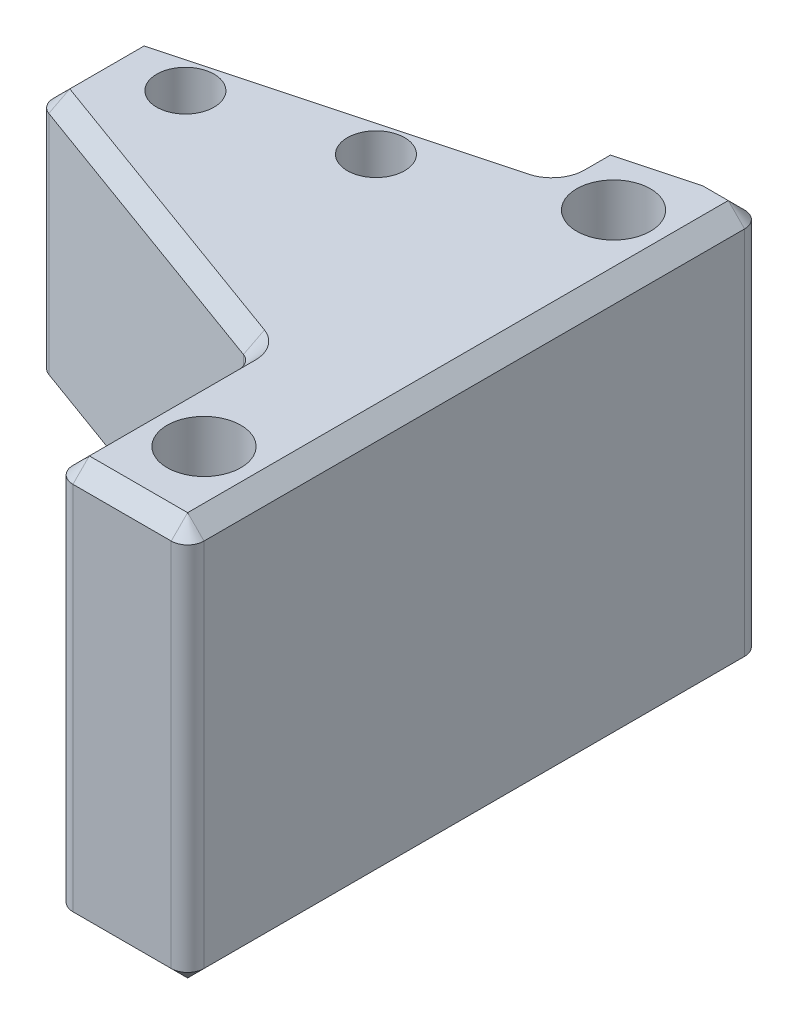
SolidWorks part; units mm, degrees
ref_plane "Front Plane" through (0, 0, 0) normal (0, 0, 1) x (1, 0, 0)
ref_plane "Top Plane" through (0, 0, 0) normal (0, 1, 0) x (1, 0, 0)
ref_plane "Right Plane" through (0, 0, 0) normal (1, 0, 0) x (0, 0, -1)
sketch "Sketch1" plane through (0, 0, 0) normal (0, 1, 0) x (1, 0, 0)
  line L1 (4, -17.5) -> (-4, -17.5)
  line L2 (4, -17.5) -> (4, 17.5)
  line L3 (4, 17.5) -> (-4, 17.5)
  line L4 (-4, -17.5) -> (-4, 17.5)
  line L5 (0, 17.5) -> (0, -17.5) construction
  line L6 (4, 0) -> (-4, 0) construction
  circle A0 centre (0, 12.5) radius 2.25
  circle A1 centre (0, -12.5) radius 2.25
  point P0 (0, 0)
  dimension "D3" = 4.5
  dimension "D1" = 25
  dimension "D2" = 8
  dimension "D4" = 35
extrude "Boss-Extrude1" add sketch "Sketch1" along normal blind 10
sketch "Sketch2" plane through (0, 10, 0) normal (0, 1, 0) x (1, 0, 0)
  line L0 (-8, 15) -> (1.3301, 17.5) construction
  line L1 (0, 14.75) -> (0, 10.25) construction
  line L2 (0, 12.5) -> (2.25, 12.5) construction
  line L3 (-8, 15) -> (-8, -17.5) construction
  line L4 (-8, -17.5) -> (-4, -17.5) construction
  line L5 (4, 17.5) -> (-4, 17.5) construction
  line L6 (-19.3763, 5.7401) -> (-10.2, 8.1989) construction
  line L7 (-4, 17.5) -> (-4, -17.5) construction
  line L8 (-4, -5.6724) -> (-24, 1.607)
  line L9 (-24, 1.607) -> (-24, 7.607)
  line L10 (-24, 7.607) -> (-4, 12.966)
  line L11 (-4, 12.966) -> (-4, -5.6724)
  line L12 (1.3301, 17.5) -> (-4, 17.5)
  line L13 (-4, 17.5) -> (-4, 16.0718)
  line L14 (-4, 16.0718) -> (1.3301, 17.5)
  circle A0 centre (0, 12.5) radius 2.25 construction
  circle A1 centre (-10.2, 8.1989) radius 1.75
  circle A2 centre (-19.3763, 5.7401) radius 1.75
  point P7 (0, 12.5)
  point P23 (-4, 0)
  point P29 (0, 0)
  point P30 (-4, -2.9492)
  point P31 (-21.9255, 6.9595)
  point P32 (-4, -4.1892)
  line M11 (-4, 17.5) -> (-4, -17.5)
  line M14 (4, 17.5) -> (-4, 17.5)
  dimension "D6" = 3.5
  dimension "D1" = 2.5
  dimension "D2" = 8
  dimension "D3" = 105
  dimension "D4" = 9.5
  dimension "D5" = 6
  dimension "D7" = 6.2
  dimension "D8" = 3
  dimension "D9" = 6
  dimension "D10" = 20
  dimension "D11" = 70
extrude "Boss-Extrude2" add sketch "Sketch2" against normal through all contours L10 L9 L8 A2 A1 M11 region at (-12.0785, 10, -3.797)
extrude "Cut-Extrude1" cut sketch "Sketch2<3>" against normal blind 10 contours L14 M11 M14 region at (-2.2233, 10, -17.0239)
sketch "Sketch2<3>" plane through (0, 10, 0) normal (0, 1, 0) x (1, 0, 0) same geometry as "Sketch2"
sketch "Sketch3" plane through (0, 10, 0) normal (0, 1, 0) x (1, 0, 0)
  line L0 (-4, 16.0718) -> (-4, -17.5)
  line L1 (-4, -17.5) -> (4, -17.5)
  line L2 (4, -17.5) -> (4, 17.5)
  line L3 (4, 17.5) -> (1.3301, 17.5)
  line L4 (-4, 16.0718) -> (1.3301, 17.5) construction
  line L5 (4, 17.5) -> (1.3301, 17.5) construction
  line L6 (1.3301, 17.5) -> (-4, 16.0718)
  circle A0 centre (0, -12.5) radius 2.25 construction
  circle A1 centre (0, 12.5) radius 2.25 construction
  circle A2 centre (0, -12.5) radius 2.25
  circle A3 centre (0, 12.5) radius 2.25
extrude "Boss-Extrude3" add sketch "Sketch3" along normal blind 6
sketch "Sketch5" plane through (0, 0, 0) normal (0, -1, 0) x (1, 0, 0)
  line L0 (-4, 17.5) -> (-4, -16.0718)
  line L1 (-4, -16.0718) -> (1.3301, -17.5)
  line L2 (1.3301, -17.5) -> (4, -17.5)
  line L3 (4, -17.5) -> (4, 17.5)
  line L4 (4, 17.5) -> (-4, 17.5)
  circle A0 centre (0, -12.5) radius 2.25 construction
  circle A1 centre (0, 12.5) radius 2.25 construction
  circle A2 centre (0, -12.5) radius 2.25
  circle A3 centre (0, 12.5) radius 2.25
extrude "Boss-Extrude5" add sketch "Sketch5" along normal blind 9
sketch "Sketch6" plane through (4, 0, 0) normal (1, 0, 0) x (0, 0, -1)
  line L2 (-17.5, 15.8) -> (17.5, 15.8)
  line L3 (-17.5, 15.8) -> (17.5, 15.8)
  line L4 (17.5, -9) -> (-17.5, -9) construction
  line L5 (17.5, -8.8) -> (-17.5, -8.8)
  line L6 (17.5, -8.8) -> (-17.5, -8.8)
  line L7 (17.5, 16) -> (17.5, -9) construction
  line L8 (-17.5, 16) -> (-17.5, -9) construction
  line L9 (-17.5, 16) -> (17.5, 16) construction
  line L10 (17.5, -9) -> (-17.5, -9)
  line L11 (17.5, 16) -> (17.5, 15.8)
  line L12 (-17.5, 16) -> (-17.5, 15.8)
  line L13 (-17.5, 16) -> (17.5, 16)
  line L14 (17.5, -8.8) -> (17.5, -9)
  line L15 (-17.5, -8.8) -> (-17.5, -9)
  dimension "D1" = 0.2
  dimension "D2" = 0.2
extrude "Cut-Extrude2" cut sketch "Sketch6" against normal up to next
sketch "Sketch8" plane through (0, 10, 0) normal (0, 1, 0) x (1, 0, 0)
  line L4 (-4, -5.6724) -> (-4, 12.966)
  line L5 (-4, 12.966) -> (-24, 7.607)
  line L6 (-24, 7.607) -> (-24, 1.607)
  line L7 (-24, 1.607) -> (-4, -5.6724)
  line L8 (-4, -5.6724) -> (-4, 12.966)
  line L9 (-4, 12.966) -> (-24, 7.607)
  line L10 (-24, 7.607) -> (-24, 1.607)
  line L11 (-24, 1.607) -> (-4, -5.6724)
  circle A0 centre (-10.2, 8.1989) radius 1.75 construction
  circle A1 centre (-19.3763, 5.7401) radius 1.75 construction
  circle A2 centre (-10.2, 8.1989) radius 1.75
  circle A3 centre (-19.3763, 5.7401) radius 1.75
  dimension "D1" = 0
extrude "Boss-Extrude6" add sketch "Sketch8" along normal up to surface (5.8 mm away) up to face at (0, 15.8, -14.75)
sketch "Sketch9" plane through (-3.5094, 0, -13.0974) normal (-0.2588, 0, -0.9659) x (-0.9659, 0, 0.2588)
  line L0 (9.4804, 6.4) -> (5.9804, 6.4) construction
  line L1 (9.4804, 0) -> (9.4804, 15.8) construction
  line L2 (5.9804, 15.8) -> (5.9804, 0) construction
  line L3 (15.4804, 6.4) -> (18.9804, 6.4) construction
  line L4 (15.4804, 15.8) -> (15.4804, 0) construction
  line L5 (18.9804, 0) -> (18.9804, 15.8) construction
  line L6 (21.2134, 0) -> (0.5079, 0) construction
  line L7 (10.5804, 5) -> (4.8804, 5)
  line L8 (10.5804, 5) -> (10.5804, 7.8)
  line L9 (10.5804, 7.8) -> (4.8804, 7.8)
  line L10 (4.8804, 5) -> (4.8804, 7.8)
  line L11 (7.7304, 7.8) -> (7.7304, 5) construction
  line L12 (10.5804, 6.4) -> (4.8804, 6.4) construction
  line L13 (20.0804, 5) -> (14.3804, 5)
  line L14 (20.0804, 5) -> (20.0804, 7.8)
  line L15 (20.0804, 7.8) -> (14.3804, 7.8)
  line L16 (14.3804, 5) -> (14.3804, 7.8)
  line L17 (17.2304, 7.8) -> (17.2304, 5) construction
  line L18 (20.0804, 6.4) -> (14.3804, 6.4) construction
  point P12 (7.7304, 6.4)
  point P16 (17.2304, 6.4)
  dimension "D1" = 5.7
  dimension "D2" = 2.8
  dimension "D3" = 5
extrude "Cut-Extrude3" cut sketch "Sketch9" against normal blind 7
fillet "Fillet1" radius 1 12 edges at (-17.3999, 6.4, -9.3755) (-13.7293, 6.4, -10.359) (-8.2236, 6.4, -11.8343) (-24, 7.9, -7.607) (-24, 7.9, -1.607) (-4, 7.9, 5.6724) (-4, 3.5, 17.5) (4, 3.5, 17.5) (4, 3.5, -17.5) (1.3301, 3.5, -17.5) (-4, 7.9, -12.966) (-4, 3.5, -16.0718)
fillet "Fillet2" radius 1 1 edges at (-22.9056, 6.4, -7.9002)
chamfer "Chamfer1" distance 1 angle 45 18 edges at (3.7071, 15.8, 17.2071) (0, 15.8, 17.5) (4, 15.8, 0) (-3.7071, 15.8, 17.2071) (3.7071, 15.8, -17.2071) (-4, 15.8, 11.4363) (2.2309, 15.8, -17.5) (-4.1808, 15.8, 5.7991) (1.3313, 15.8, -17.4914) (-14, 15.8, 2.0327) (-1.0279, 15.8, -16.8682) (-23.8192, 15.8, -1.7336) (-3.7934, 15.8, -15.9132) (-24, 15.8, -4.5734) (-4, 15.8, -14.5189) (-23.7934, 15.8, -7.4484) (-4.2066, 15.8, -13.1245) (-14, 15.8, -10.2865)
chamfer "Chamfer2" distance 1 angle 45 17 edges at (-4.1808, 0, 5.7991) (-14, 0, 2.0327) (-23.8192, 0, -1.7336) (-24, 0, -4.5734) (-23.7934, 0, -7.4484) (-4.2066, 0, -13.1245) (-14, 0, -10.2865) (3.7071, -8.8, -17.2071) (4, -8.8, 0) (2.2309, -8.8, -17.5) (3.7071, -8.8, 17.2071) (1.3313, -8.8, -17.4914) (0, -8.8, 17.5) (-1.0279, -8.8, -16.8682) (-3.7071, -8.8, 17.2071) (-3.7934, -8.8, -15.9132) (-4, -8.8, 0.5978)
